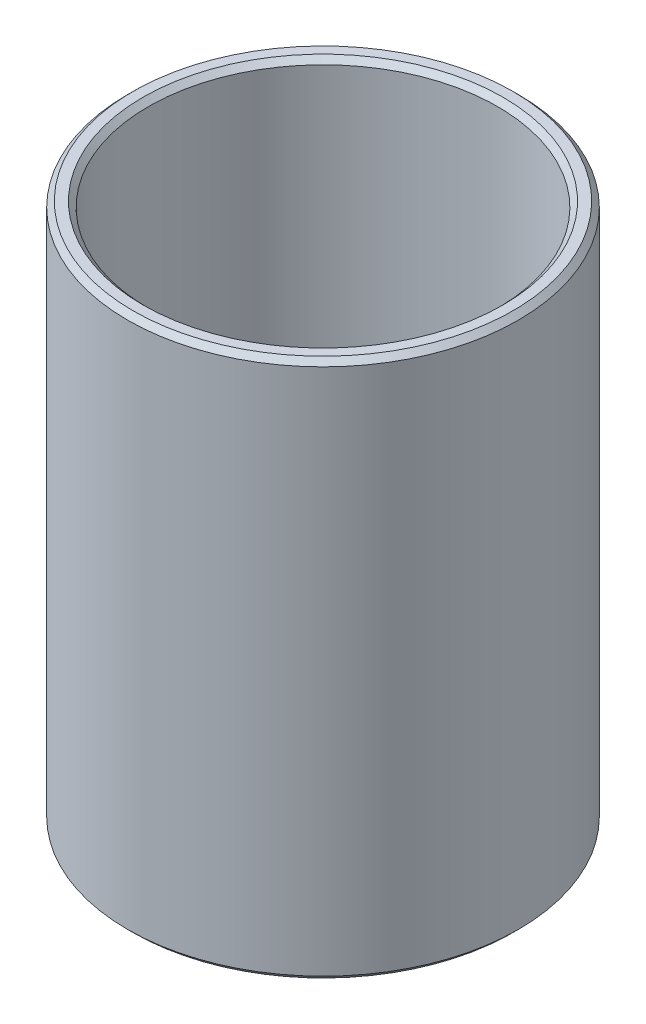
SolidWorks part; units mm, degrees
ref_plane "Front Plane" through (0, 0, 0) normal (0, 0, 1) x (1, 0, 0)
ref_plane "Top Plane" through (0, 0, 0) normal (0, 1, 0) x (1, 0, 0)
ref_plane "Right Plane" through (0, 0, 0) normal (1, 0, 0) x (0, 0, -1)
sketch "Sketch1" plane through (0, 0, 0) normal (0, 1, 0) x (1, 0, 0)
  circle A0 centre (0, 0) radius 60
  dimension "SLEEVE_OD" = 120
extrude "Boss-Extrude1" add sketch "Sketch1" along normal blind 165.3582
sketch "Sketch2" plane through (0, 0, 0) normal (0, 1, 0) x (1, 0, 0)
  circle A0 centre (0, 0) radius 53.6116
  dimension "BORE_D" = 107.2232
extrude "Cut-Extrude1" cut sketch "Sketch2" along normal through all
chamfer "Chamfer1" distance 1.661 angle 45 4 edges at (0, 165.3582, 53.6116) (0, 0, 53.6116) (0, 0, 60) (0, 165.3582, 60)
